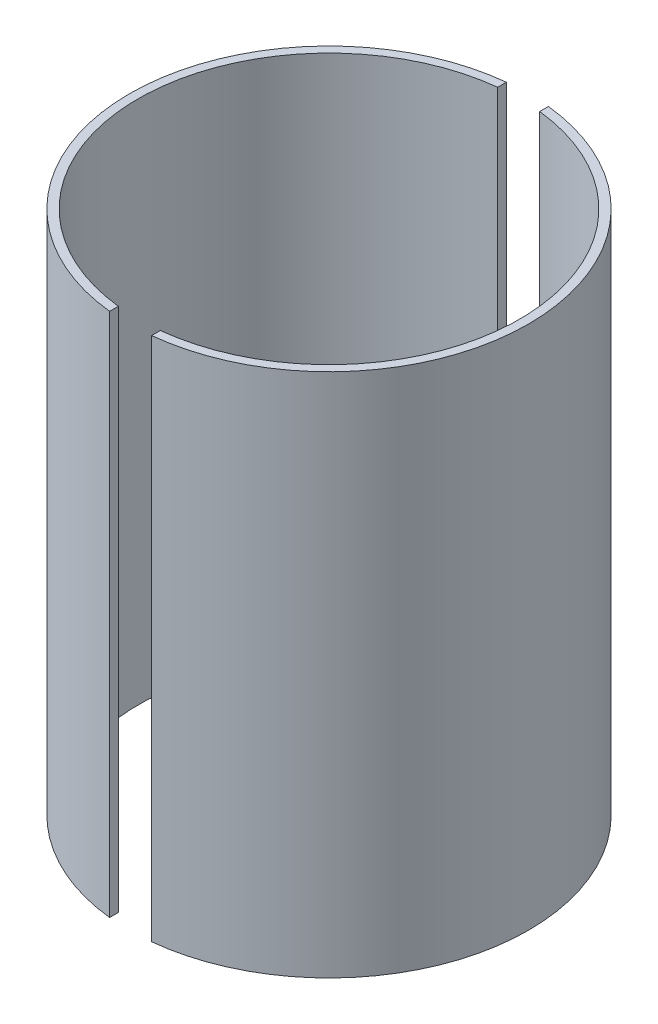
SolidWorks part; units mm, degrees
ref_plane "Plan de face" through (0, 0, 0) normal (0, 0, 1) x (1, 0, 0)
ref_plane "Plan de dessus" through (0, 0, 0) normal (0, 1, 0) x (1, 0, 0)
ref_plane "Plan de droite" through (0, 0, 0) normal (1, 0, 0) x (0, 0, -1)
sketch "Esquisse1" plane through (0, 0, 0) normal (0, 1, 0) x (1, 0, 0)
  circle A0 centre (0, 0) radius 76
  circle A1 centre (0, 0) radius 72.7
  dimension "D1" = 152
  dimension "D2" = 3.3
extrude "Boss.-Extru.1" add sketch "Esquisse1" along normal blind 200
ref_plane "Plan1" through (0, 100, 0) normal (0, -1, 0) x (-1, 0, 0)
sketch "Esquisse2" plane through (0, 0, 0) normal (0, -1, 0) x (1, 0, 0)
  line L0 (-8, -59.009) -> (-8, -72.009) construction
  line L1 (-8, 125.8717) -> (8, 125.8717)
  line L2 (-8, 125.8717) -> (-8, -81.6265)
  line L3 (-8, -81.6265) -> (8, -81.6265)
  line L4 (8, 125.8717) -> (8, -81.6265)
  line L5 (8, -72.009) -> (8, -59.009) construction
extrude "Enlèv. mat.-Extru.1" cut sketch "Esquisse2" against normal through all
